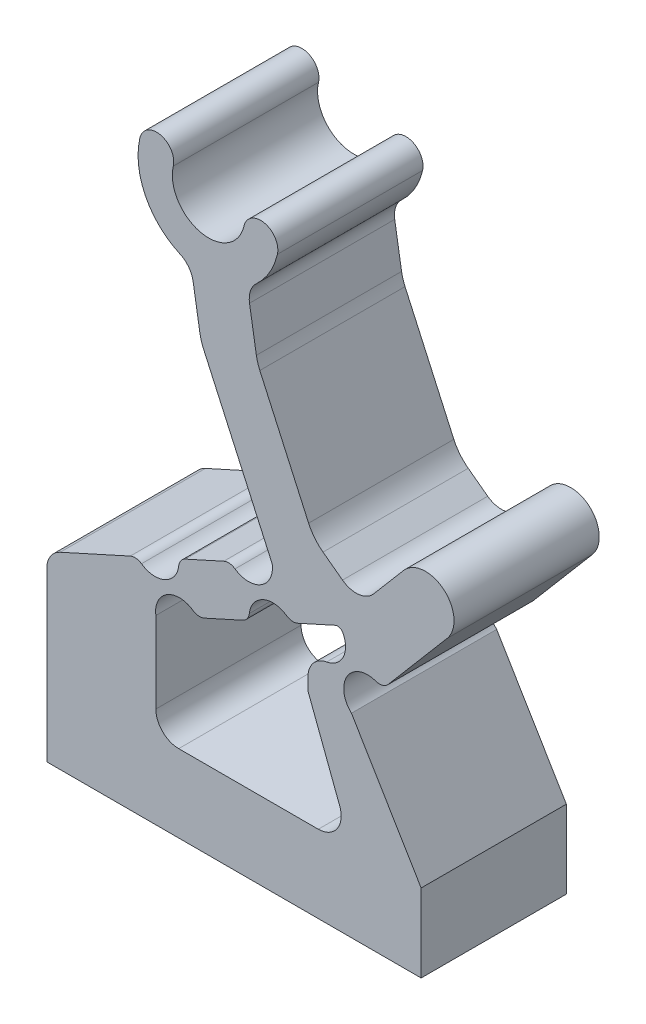
SolidWorks part; units mm, degrees
ref_plane "Front Plane" through (0, 0, 0) normal (0, 0, 1) x (1, 0, 0)
ref_plane "Top Plane" through (0, 0, 0) normal (0, 1, 0) x (1, 0, 0)
ref_plane "Right Plane" through (0, 0, 0) normal (1, 0, 0) x (0, 0, -1)
sketch "Sketch-SkeletonConfigUp" plane through (0, 0, 0) normal (0, 0, 1) x (1, 0, 0)
  line L0 (0, 0) -> (0, -50000) construction
  line L1 (0, 0) -> (5.2694, -4.2823) construction
  line L2 (16.5608, -13.4586) -> (13.0191, -3.4572) construction
  line L3 (13.0191, -3.4572) -> (9.3602, -2.4315) construction
  line L4 (9.3602, -2.4315) -> (5.2694, -4.2823) construction
  line L5 (13.0191, -3.4572) -> (16.5614, 0.711) construction
  line L6 (9.3602, -2.4315) -> (7.0797, 11.4322) construction
  line L7 (5.2694, -4.2823) -> (16.5608, -13.4586) construction
  line L8 (-768.3403, 624.4132) -> (16.5608, -13.4586) construction
  dimension "D2" = 6.79
  dimension "D3" = 14.55
  dimension "D4" = 10.61
  dimension "D5" = 148.6
  dimension "D6" = 3.8
  dimension "D7" = 5.47
  dimension "D8" = 14.05
  dimension "D9" = 4.49
  dimension "D10" = 65.3
  dimension "D11" = 65
  dimension "D12" = 50.9
sketch "Sketch-SkeletonConfigDown" plane through (0, 0, 0) normal (0, 0, 1) x (1, 0, 0)
  line L0 (0, 0) -> (0, -50000) construction
  line L1 (0, 0) -> (5.2694, -4.2823) construction
  line L2 (16.5608, -13.4586) -> (13.0191, -3.4572) construction
  line L3 (13.0191, -3.4572) -> (9.6581, -5.2302) construction
  line L4 (9.6581, -5.2302) -> (5.2694, -4.2823) construction
  line L5 (13.0191, -3.4572) -> (12.7221, 2.0047) construction
  line L6 (9.6581, -5.2302) -> (-1.5351, 3.2618) construction
  line L7 (5.2694, -4.2823) -> (16.5608, -13.4586) construction
  line L8 (-771.7106, 627.1522) -> (16.5608, -13.4586) construction
  dimension "D2" = 6.79
  dimension "D3" = 14.55
  dimension "D4" = 10.61
  dimension "D5" = 148.6
  dimension "D6" = 3.8
  dimension "D7" = 5.47
  dimension "D8" = 14.05
  dimension "D9" = 4.49
  dimension "D10" = 65.3
  dimension "D11" = 65
  dimension "D1" = 50.9
sketch "Sketch-ConfigUp" plane through (0, 0, 0) normal (0, 0, 1) x (1, 0, 0)
  line L1 (8.0369, -1.9326) -> (5.7683, -2.959)
  line L4 (9.3602, -2.4315) -> (5.2694, -4.2823) construction
  line L5 (15.6089, 1.5204) -> (13.6856, -0.7427)
  line L6 (5.2694, -4.2823) -> (16.5608, -13.4586) construction
  line L9 (13.0191, -3.4572) -> (9.3602, -2.4315) construction
  line L11 (6.9026, -2.4458) -> (7.727, -4.268) construction
  line L16 (13.3241, -5.0287) -> (14.6192, -3.5047) construction
  line L17 (17.5139, -0.0985) -> (14.6721, -3.4424)
  line L18 (13.0191, -3.4572) -> (16.5614, 0.711) construction
  line L19 (15.6013, 1.5115) -> (17.5063, -0.1075) construction
  line L20 (6.3045, 8.4436) -> (6.7426, 5.7803)
  line L21 (9.2095, 6.186) -> (8.7714, 8.8493)
  line L22 (9.3602, -2.4315) -> (7.0797, 11.4322) construction
  line L23 (6.0231, 10.1543) -> (8.49, 10.5601) construction
  line L26 (12.3716, -4.2192) -> (9.4385, -7.6705) construction
  line L27 (-155977.6217, 126759.5747) -> (16.5608, -13.4586) construction
  line L30 (10.3474, -5.0569) -> (11.8714, -6.352) construction
  line L38 (5.5133, 11.1745) -> (7.0797, 11.4322) construction
  line L39 (7.0797, 11.4322) -> (10.0861, 10.7293) construction
  line L42 (7.2022, -8.5173) -> (7.2022, -13.5356) construction
  line L43 (12.7142, -1.8857) -> (14.6192, -3.5047) construction
  line L44 (6.1805, -3.8701) -> (4.3583, -4.6945) construction
  line L46 (6.5926, -4.7812) -> (4.7705, -5.6056) construction
  line L47 (11.4191, -3.4097) -> (13.3241, -5.0287) construction
  line L51 (9.2571, -2.2038) -> (9.4632, -2.6593) construction
  line L52 (8.0369, -1.9326) -> (8.8613, -3.7548) construction
  line L53 (9.8591, -1.1082) -> (10.6835, -2.9304) construction
  line L54 (6.1549, -10.1498) -> (6.1549, -13.5356) construction
  line L56 (8.4491, -2.8437) -> (10.2713, -2.0193) construction
  line L59 (9.8591, -1.1082) -> (8.0369, -1.9326) construction
  line L61 (8.8613, -3.7548) -> (6.5926, -4.7812)
  line L62 (5.7683, -2.959) -> (6.5926, -4.7812) construction
  line L67 (7.0797, 11.4322) -> (4.0733, 12.135) construction
  line L69 (13.2096, -3.6191) -> (12.8286, -3.2953) construction
  line L71 (14.6192, -3.5047) -> (15.6685, -2.2699) construction
  line L73 (5.7683, -2.959) -> (3.9461, -3.7834) construction
  line L77 (9.4385, -7.6705) -> (16.5608, -13.4586) construction
  line L81 (12.3716, -4.2192) -> (13.6667, -2.6952) construction
  line L82 (15.6013, 1.5115) -> (13.6856, -0.7427) construction
  line L93 (5.1663, -4.0545) -> (5.3724, -4.5101) construction
  line L108 (0, -5.5687) -> (0, -13.5356)
  line L109 (0, -13.5356) -> (13.3241, -13.5356)
  line L115 (3.9461, -3.7834) -> (0, -5.5687)
  line L117 (11.4191, -3.4097) -> (12.7142, -1.8857) construction
  line L121 (10.6835, -2.9304) -> (8.8613, -3.7548) construction
  line L125 (4.7705, -5.6056) -> (4.7705, -10.1498)
  line L129 (3.9461, -3.7834) -> (4.7705, -5.6056) construction
  line L131 (0, -10.1498) -> (16.3859, -10.1498) construction
  line L132 (0, 200000) -> (0, -250000) construction
  line L133 (13.3241, -5.0287) -> (13.3241, -10.1498) construction
  line L134 (11.4191, -3.4097) -> (11.4191, -5.1284)
  line L135 (11.4191, -10.1498) -> (6.1549, -10.1498)
  line L136 (13.3241, -10.1498) -> (13.3241, -13.5356) construction
  line L137 (4.7705, -10.1498) -> (6.1549, -10.1498)
  line L138 (13.6856, -0.7427) -> (12.7142, -1.8857) construction
  line L140 (13.3241, -5.0287) -> (16.3721, -10.1267)
  line L141 (16.3721, -10.1267) -> (16.3721, -13.5356)
  line L142 (16.3721, -13.5356) -> (13.3241, -13.5356)
  line L143 (11.4191, -5.1284) -> (13.3241, -10.1498)
  line L144 (13.3241, -10.1498) -> (11.4191, -10.1498)
  line L145 (11.4191, -5.1284) -> (11.4191, -10.1498) construction
  line L146 (9.8591, -1.1082) -> (12.7142, -1.8857) construction
  line L149 (11.6652, 0.7579) -> (13.6856, -0.7427)
  line L152 (10.6835, -2.9304) -> (12.8032, -1.9714)
  line L154 (9.8591, -1.1082) -> (6.7426, 5.7803)
  line L156 (6.7426, 5.7803) -> (9.2095, 6.186) construction
  line L157 (9.2095, 6.186) -> (11.6652, 0.7579)
  arc A0 (15.6089, 1.5204) -> (17.5139, -0.0985) centre (16.5614, 0.711) cw
  arc A2 (5.5339, 11.7936) -> (8.6255, 11.0708) centre (7.0797, 11.4322) ccw
  arc A3 (8.7714, 8.8493) -> (10.0861, 10.7293) centre (7.0797, 11.4322) ccw
  arc A4 (4.0733, 12.135) -> (5.5339, 11.7936) centre (4.8036, 11.9643) cw
  arc A5 (10.0861, 10.7293) -> (8.6255, 11.0708) centre (9.3558, 10.9) ccw
  arc A6 (4.0733, 12.135) -> (6.3045, 8.4436) centre (7.0797, 11.4322) ccw
  arc A7 (8.8613, -3.7548) -> (10.6835, -2.9304) centre (9.8926, -3.6084) cw
  arc A15 (6.5926, -4.7812) -> (4.7705, -5.6056) centre (5.8018, -5.4591) ccw
  arc A21 (8.0369, -1.9326) -> (9.8591, -1.1082) centre (8.8278, -1.2547) ccw
  arc A42 (5.7683, -2.959) -> (3.9461, -3.7834) centre (4.7369, -3.1055) cw
  arc A43 (13.3241, -5.0287) -> (14.6721, -3.4424) centre (14.0292, -4.262) cw
  arc A44 (11.4191, -3.4097) -> (12.8032, -1.9714) centre (12.0666, -2.6477) ccw
  point P27 (7.3148, -3.3569)
  point P28 (11.2393, 0.3017)
  point P38 (16.5538, 0.702)
  point P51 (7.2565, 10.3572)
  point P61 (11.1094, -5.7044)
  point P125 (5.3724, -4.5101)
  point P130 (5.1663, -4.0545)
  dimension "D3" = 3.175
  dimension "D4" = 6.175
  dimension "D5" = 1.5
  dimension "D6" = 2
  dimension "D10" = 2
  dimension "D14" = 22.5
  dimension "D16" = 2.5
  dimension "D21" = 22.5
  dimension "D11" = 0.5
  dimension "D7" = 0.5
  dimension "D9" = 2
  dimension "D22" = 2
  dimension "D24" = 0.5
extrude "Boss-ConfigUp" add sketch "Sketch-ConfigUp" along normal blind 6.35
fillet "Fillet1" radius 1 4 edges at (8.7714, 8.8493, 3.175) (6.3045, 8.4436, 3.175) (0, -5.5687, 3.175) (13.6856, -0.7427, 3.175)
fillet "Fillet2" radius 1 1 edges at (11.4191, -3.4097, 3.175)
fillet "Fillet3" radius 0.5 7 edges at (14.6721, -3.4424, 3.175) (3.9461, -3.7834, 3.175) (6.5926, -4.7812, 3.175) (8.8613, -3.7548, 3.175) (8.0369, -1.9326, 3.175) (5.7683, -2.959, 3.175) (10.6835, -2.9304, 3.175)
fillet "Fillet4" radius 0.25 2 edges at (9.8591, -1.1082, 3.175) (12.8032, -1.9714, 3.175)
fillet "Fillet5" radius 2 3 edges at (11.6652, 0.7579, 3.175) (9.2095, 6.186, 3.175) (6.7426, 5.7803, 3.175)
fillet "Fillet7" radius 1 2 edges at (13.3241, -10.1498, 3.175) (4.7705, -10.1498, 3.175)
equation "\"axle-diameter\"=2"
equation "\"switch-thickness\"=12"
equation "\"base-width\"=4.0"
equation "\"axle-bushing-radius\"=3"
equation "\"clearance\"= 0.25"
equation "\"arm-width\"=1.5"
equation "\"min-diameter\"=70"
equation "\"alpha\"=50.9"
equation "\"beta\"=26.83"
equation "\"gamma\"=148.6"
equation "\"delta\"=65.0"
equation "\"epsilon\"=65.3"
equation "\"eta\"=-261.68"
equation "\"l_AB\"=14.55"
equation "\"l_AC\"=4.49"
equation "\"l_BD\"=10.61"
equation "\"l_CD\"=3.80"
equation "\"l_CE\"=14.05"
equation "\"l_DF\"=5.47"
equation "\"l_OA\"=6.79"
equation "\"D2@Sketch-SkeletonConfigUp\" = \"l_OA\""
equation "\"D3@Sketch-SkeletonConfigUp\" = \"l_AB\""
equation "\"D4@Sketch-SkeletonConfigUp\" = \"l_BD\""
equation "\"D5@Sketch-SkeletonConfigUp\" = \"gamma\""
equation "\"D6@Sketch-SkeletonConfigUp\" = \"l_CD\""
equation "\"D7@Sketch-SkeletonConfigUp\" = \"l_DF\""
equation "\"D8@Sketch-SkeletonConfigUp\" = \"l_CE\""
equation "\"D9@Sketch-SkeletonConfigUp\" = \"l_AC\""
equation "\"D_groove\"=3.175"
equation "\"D7@Sketch-SkeletonConfigDown\" = \"l_DF\""
equation "\"D6@Sketch-SkeletonConfigDown\" = \"l_CD\""
equation "\"D2@Sketch-SkeletonConfigDown\" = \"l_OA\""
equation "\"D3@Sketch-SkeletonConfigDown\" = \"l_AB\""
equation "\"D9@Sketch-SkeletonConfigDown\" = \"l_AC\""
equation "\"D8@Sketch-SkeletonConfigDown\" = \"l_CE\""
equation "\"D5@Sketch-SkeletonConfigDown\" = \"gamma\""
equation "\"D4@Sketch-SkeletonConfigDown\" = \"l_BD\""
equation "\"D1@Sketch-SkeletonConfigDown\" = \"alpha\""
equation "\"hinge_length\"=1.5"
equation "\"hinge_depth\"=0.25"
equation "\"D10@Sketch-SkeletonConfigUp\"=\"epsilon\""
equation "\"D11@Sketch-SkeletonConfigUp\"=\"delta\""
equation "\"D12@Sketch-SkeletonConfigUp\"=\"alpha\""
equation "\"D11@Sketch-SkeletonConfigDown\"=\"delta\""
equation "\"D10@Sketch-SkeletonConfigDown\"=\"epsilon\""
equation "\"EE_dx\"=8.64"
equation "\"EE_dy\"=8.19"
equation "\"r_groove\"=\"D_groove\"/2"
equation "\"t_wall\"=25.4/16"
equation "\"width_lower\"=\"D_groove\"+\"t_wall\""
equation "\"cable_to_bottom\"=30.6257"
